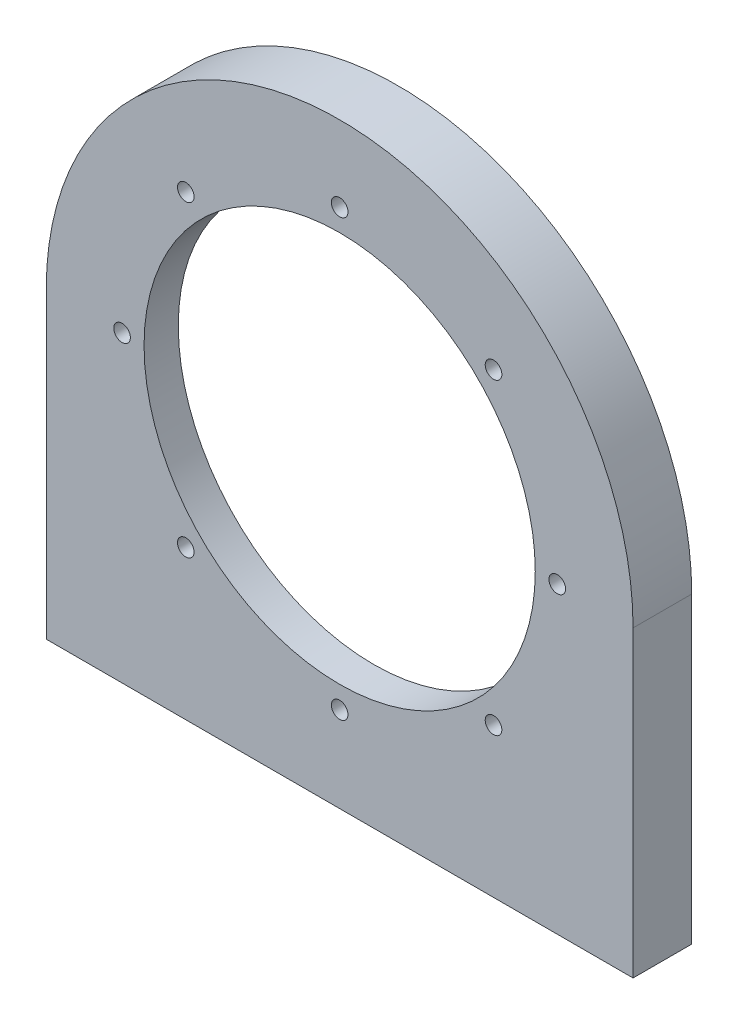
SolidWorks part; units mm, degrees
material "6063-T6"
ref_plane "Front Plane" through (0, 0, 0) normal (0, 0, 1) x (1, 0, 0)
ref_plane "Top Plane" through (0, 0, 0) normal (0, 1, 0) x (1, 0, 0)
ref_plane "Right Plane" through (0, 0, 0) normal (1, 0, 0) x (0, 0, -1)
sketch "Sketch1" plane through (0, 0, 0) normal (0, 0, 1) x (1, 0, 0)
  circle A0 centre (0, 0) radius 60
  circle A1 centre (0, 0) radius 40
  dimension "D1" = 120
  dimension "D2" = 80
extrude "Boss-Extrude1" add sketch "Sketch1" along normal blind 7
sketch "Sketch2" plane through (0, 0, 7) normal (0, 0, 1) x (1, 0, 0)
  circle A0 centre (0, 0) radius 44.5 construction
  point P5 (0, 44.5)
  point P13 (31.4663, 31.4663)
  point P14 (44.5, 0)
  point P15 (31.4663, -31.4663)
  point P16 (0, -44.5)
  point P17 (-31.4663, -31.4663)
  point P18 (-44.5, 0)
  point P19 (-31.4663, 31.4663)
  dimension "D1" = 89
  dimension "D2" = 8
hole_wizard "M3 Clearance Hole1" positions "Sketch2" profile "Sketch3" hole size "M3" standard "DIN" end condition through all
sketch "Sketch3" plane through (-31.4663, 31.4663, 7) normal (1, 0, 0) x (0, -1, 0)
  line L0 (0, 0) -> (0, 7)
  line L1 (0, 7) -> (1.7, 7)
  line L2 (1.7, 7) -> (1.7, 0)
  line L5 (1.7, 0) -> (0, 0)
  line L11 (0, -6.35) -> (0, 107.95) construction
  dimension "Thru Hole Dia." = 3.4
  dimension "Thru Hole Depth" = 7
sketch "Sketch4" plane through (0, 0, 0) normal (0, 0, -1) x (-1, 0, 0)
  circle A0 centre (0, 0) radius 50
  circle A1 centre (0, 0) radius 60 construction
  circle A2 centre (0, 0) radius 60
  dimension "D1" = 100
extrude "Boss-Extrude3" add sketch "Sketch4" along normal blind 5
sketch "Sketch5" plane through (0, 0, 7) normal (0, 0, 1) x (1, 0, 0)
  line L0 (-60, 0) -> (-60, -62)
  line L1 (-60, -62) -> (60, -62)
  line L2 (60, -62) -> (60, 0)
  circle A0 centre (0, 0) radius 60 construction
  arc A1 (-60, 0) -> (60, 0) centre (0, 0) ccw
  dimension "D1" = 62
extrude "Boss-Extrude4" add sketch "Sketch5" against normal up to surface (12 mm away) up to face at (-60, 0, -5)
sketch "Sketch7" plane through (0, -62, 0) normal (0, -1, 0) x (-1, 0, 0)
  line L0 (-60, -1) -> (60, -1) construction
  line L1 (-60, 5) -> (-60, -7) construction
  line L2 (60, 5) -> (60, -7) construction
  point P9 (0, -1)
  point P19 (25, -1)
  point P20 (50, -1)
  point P21 (0, -1)
  point P22 (25, -1)
  point P23 (-25, -1)
  point P24 (0, -1)
  point P25 (-25, -1)
  point P26 (-50, -1)
  dimension "D1" = 3
  dimension "D2" = 3
hole_wizard "Tap Drill for M4 Tap1" positions "Sketch7" profile "Sketch8" hole size "M4" standard "DIN"
sketch "Sketch8" plane through (50, -62, 1) normal (1, 0, 0) x (0, 0, -1)
  line L0 (0, 0) -> (0, 10.9914)
  line L1 (0, 10.9914) -> (1.65, 10)
  line L2 (1.65, 10) -> (1.65, 0)
  line L5 (1.65, 0) -> (0, 0)
  line L10 (0, 10.9914) -> (-1.65, 10) construction
  line L11 (0, -6.35) -> (0, 107.95) construction
  dimension "Hole Dia." = 3.3
  dimension "Hole Depth" = 10
  dimension "Drill Angle" = 118
